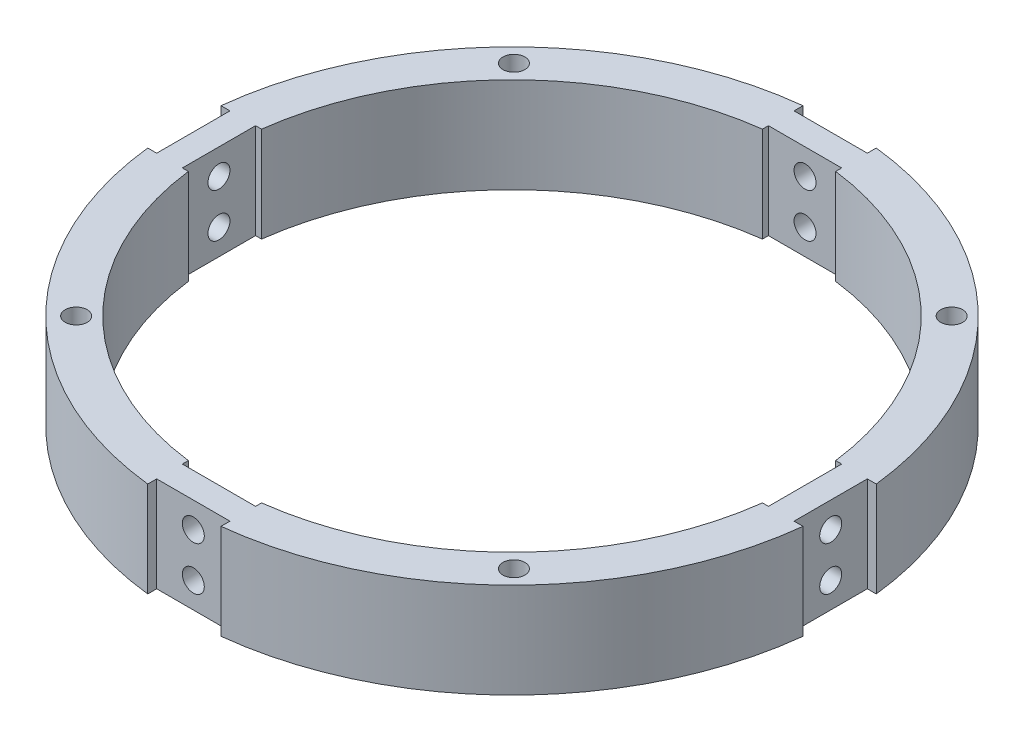
SolidWorks part; units mm, degrees
ref_plane "Front Plane" through (0, 0, 0) normal (0, 0, 1) x (1, 0, 0)
ref_plane "Top Plane" through (0, 0, 0) normal (0, 1, 0) x (1, 0, 0)
ref_plane "Right Plane" through (0, 0, 0) normal (1, 0, 0) x (0, 0, -1)
sketch "Sketch1" plane through (0, 0, 0) normal (0, 1, 0) x (1, 0, 0)
  circle A0 centre (0, 0) radius 90
  circle A1 centre (0, 0) radius 79
  dimension "OuterDiameter" = 180
  dimension "InnerDiameter" = 158
extrude "Boss-Extrude1" add sketch "Sketch1" along normal blind 13 and the other way blind 13
sketch "Sketch5" plane through (0, 13, 0) normal (0, 1, 0) x (1, 0, 0)
  line L0 (0, 0) -> (53.7588, 53.7588) construction
  line L1 (0.2616, 0.2616) -> (60.0121, 60.0121) construction
  line L2 (-121.3123, 0) -> (150.1577, 0) construction
  circle A0 centre (60.0121, 60.0121) radius 3
  circle A1 centre (60.0121, -59.4889) radius 3
  circle A2 centre (-59.4889, -59.4889) radius 3
  circle A3 centre (-59.4889, 60.0121) radius 3
  dimension "MountingBoltDiameter" = 6
  dimension "D2" = 84.5
  dimension "D3" = 45
extrude "Cut-Extrude3" cut sketch "Sketch5" against normal through all
sketch "Sketch6" plane through (0, 13, 0) normal (0, 1, 0) x (1, 0, 0)
  line L0 (0, -83.4209) -> (0, 77.0416) construction
  line L1 (-88.8703, 0) -> (103.6253, 0) construction
  line L2 (-10, -87) -> (10, -87)
  line L3 (-10, 90) -> (10, 90)
  line L4 (-10, 90) -> (-10, 87)
  line L5 (-10, 87) -> (10, 87)
  line L6 (10, 90) -> (10, 87)
  line L7 (-10, 90) -> (10, 87) construction
  line L8 (-10, 87) -> (10, 90) construction
  line L9 (10, -90) -> (10, -87)
  line L10 (-10, -90) -> (10, -90)
  line L11 (-10, -90) -> (-10, -87)
  line L12 (0, 0) -> (60.635, 60.635) construction
  line L13 (87, -10) -> (87, 10)
  line L14 (90, 10) -> (87, 10)
  line L15 (90, -10) -> (90, 10)
  line L16 (90, -10) -> (87, -10)
  line L17 (-90, -10) -> (-87, -10)
  line L18 (-90, -10) -> (-90, 10)
  line L19 (-90, 10) -> (-87, 10)
  line L20 (-87, -10) -> (-87, 10)
  point P5 (0, 88.5)
  point P10 (0, 90)
  dimension "RailWidth" = 20
  dimension "D1" = 90
  dimension "D2" = 3
extrude "Cut-Extrude4" cut sketch "Sketch6" against normal through all
sketch "Sketch7" plane through (-87, 0, 0) normal (-1, 0, 0) x (0, 0, 1)
  line L0 (0, 14.1508) -> (0, -8.7308) construction
  line L1 (-87, 0) -> (87, 0) construction
  line L2 (-87, -13) -> (-87, 13) construction
  line L3 (87, -13) -> (87, 13) construction
  circle A0 centre (0, 6) radius 3
  circle A1 centre (0, -6) radius 3
  dimension "RailBoltDiameter" = 6
  dimension "D1" = 6
extrude "Cut-Extrude5" cut sketch "Sketch7" against normal through all
sketch "Sketch12" plane through (0, 0, 87) normal (0, 0, 1) x (1, 0, 0)
  line L0 (0, 13.7216) -> (0, -16.0459) construction
  line L1 (-75.3828, 0) -> (78.5537, 0) construction
  circle A0 centre (0, 6) radius 3
  circle A1 centre (0, -6) radius 3
  dimension "D1" = 6
  dimension "D2" = 6
extrude "Cut-Extrude8" cut sketch "Sketch12" against normal through all
sketch "Sketch13" plane through (0, 13, 0) normal (0, 1, 0) x (1, 0, 0)
  line L0 (0, -87.0356) -> (0, 86.4553) construction
  line L1 (-98.9563, 0) -> (122.4152, 0) construction
  line L2 (0, 0) -> (96.5387, 96.5387) construction
  line L3 (-10, -80) -> (10, -80)
  line L4 (-10, -80) -> (-10, -77)
  line L5 (-10, -77) -> (10, -77)
  line L6 (10, -80) -> (10, -77)
  line L7 (-10, -80) -> (10, -77) construction
  line L8 (-10, -77) -> (10, -80) construction
  line L9 (-10, 77) -> (10, 77)
  line L10 (10, 80) -> (10, 77)
  line L11 (-10, 80) -> (10, 80)
  line L12 (-10, 80) -> (-10, 77)
  line L13 (-77, -10) -> (-77, 10)
  line L14 (-80, 10) -> (-77, 10)
  line L15 (-80, -10) -> (-80, 10)
  line L16 (-80, -10) -> (-77, -10)
  line L17 (80, -10) -> (77, -10)
  line L18 (80, -10) -> (80, 10)
  line L19 (80, 10) -> (77, 10)
  line L20 (77, -10) -> (77, 10)
  point P7 (0, -78.5)
  dimension "D1" = 20
  dimension "D3" = 77
  dimension "D2" = 80
  dimension "D4" = 45
extrude "Cut-Extrude9" cut sketch "Sketch13" against normal through all
equation "\"InternalDiameter\"= 158mm"
equation "\"ExternalDiameter\"= 180mm"
equation "\"InnerDiameter@Sketch1\"= \"InternalDiameter\""
equation "\"OuterDiameter@Sketch1\"= \"ExternalDiameter\""
equation "\"MountingBoltDiameter\"= 6mm"
equation "\"NumberOfMountingBolts\"= 4"
equation "\"MountingBoltDiameter@Sketch5\"= \"MountingBoltDiameter\""
equation "\"D1@Sketch5\"= \"NumberOfMountingBolts\""
equation "\"D2@Sketch5\"= 0.25 * ( \"InternalDiameter\" + \"ExternalDiameter\" )"
equation "\"RailBoltDiameter\"= 6mm"
equation "\"RailBoltDiameter@Sketch7\"= \"RailBoltDiameter\""
equation "\"D1@Sketch7\" = \"RailBoltSpacing\" / 2"
equation "\"RailBoltSpacing\"= 12mm"
equation "\"RailWidth\"= 10mm"
equation "\"RailWidth@Sketch6\"= \"RailWidth\" * 2"
equation "\"D2@Sketch12\"= \"RailBoltDiameter\""
equation "\"D1@Sketch12\"= \"RailBoltSpacing\" / 2"
equation "\"D1@Sketch13\"= \"RailWidth\" * 2"
equation "\"RailDepth\"= 2mm"
equation "\"D3@Sketch13\"= \"InternalDiameter\" / 2 - \"RailDepth\""
equation "\"D2@Sketch13\"= \"InternalDiameter\" / 2 + \"RailDepth\" / 2"
equation "\"D1@Sketch6\"= \"ExternalDiameter\" / 2"
equation "\"D2@Sketch6\"= \"RailDepth\" * 1.5"
